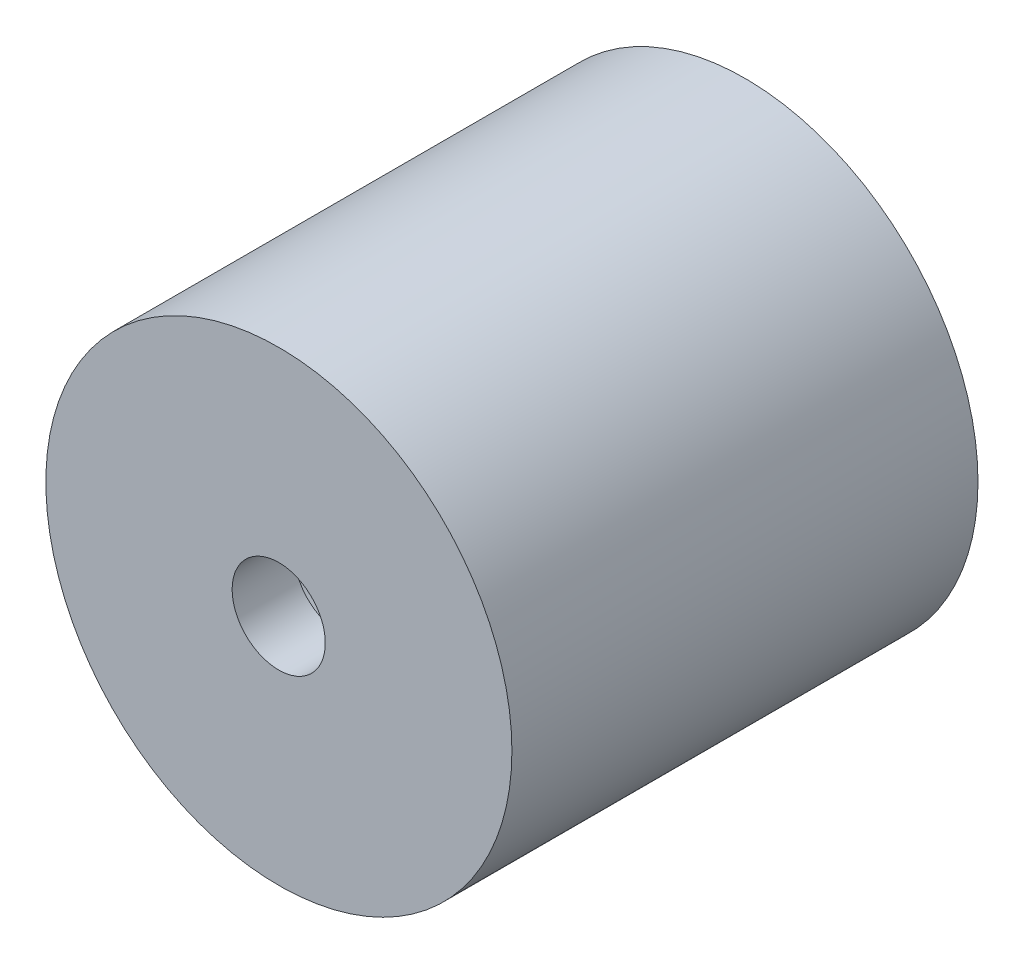
SolidWorks part; units mm, degrees
ref_plane "Front Plane" through (0, 0, 0) normal (0, 0, 1) x (1, 0, 0)
ref_plane "Top Plane" through (0, 0, 0) normal (0, 1, 0) x (1, 0, 0)
ref_plane "Right Plane" through (0, 0, 0) normal (1, 0, 0) x (0, 0, -1)
sketch "Sketch1" plane through (0, 0, 0) normal (0, 0, 1) x (1, 0, 0)
  circle A0 centre (0, 0) radius 15
  point P0 (0, 0)
  point P3 (0, 0)
  point P4 (0, 0)
extrude "Boss-Extrude1" add sketch "Sketch1" along normal blind 30
shell "Shell13" thickness 4 removed face at (15, 0, 0)
sketch "Sketch3" plane through (0, 0, 26) normal (0, 0, -1) x (-1, 0, 0)
  circle A0 centre (0.0103, 0.0076) radius 3
extrude "Cut-Extrude2" cut sketch "Sketch3" against normal blind 4
